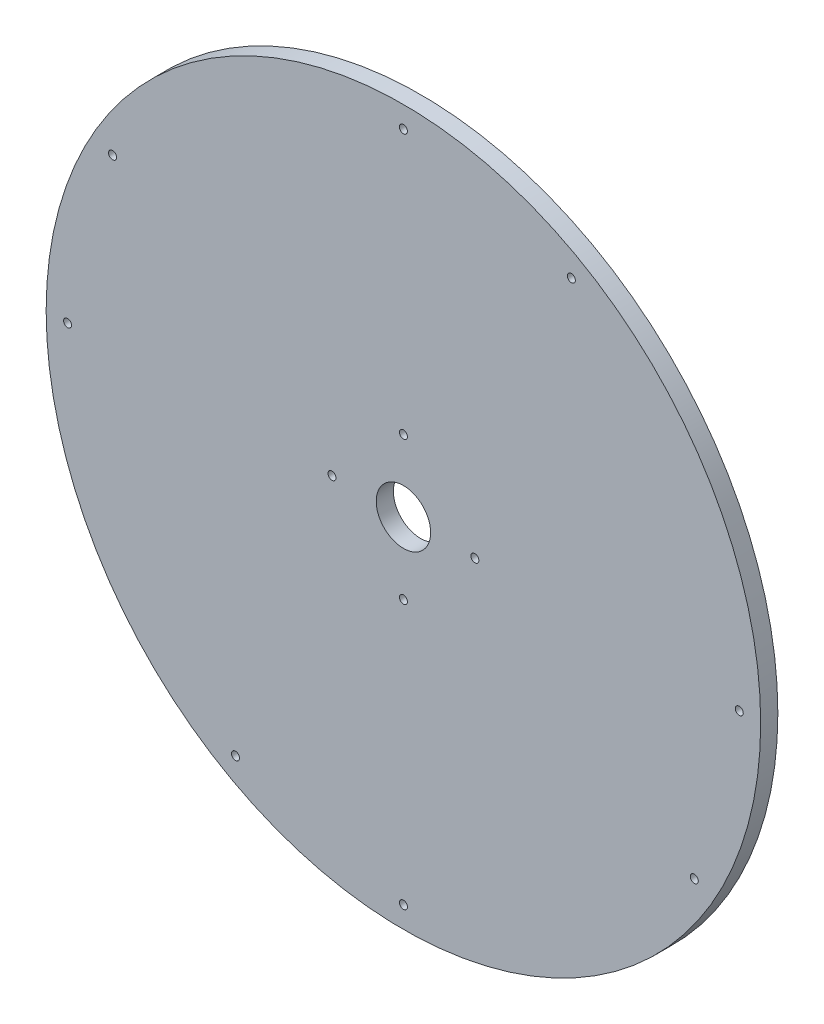
SolidWorks part; units mm, degrees
material "Pine"
ref_plane "Front Plane" through (0, 0, 0) normal (0, 0, 1) x (1, 0, 0)
ref_plane "Top Plane" through (0, 0, 0) normal (0, 1, 0) x (1, 0, 0)
ref_plane "Right Plane" through (0, 0, 0) normal (1, 0, 0) x (0, 0, -1)
sketch "Sketch1" plane through (0, 0, 0) normal (1, 0, 0) x (0, 0, -1)
  line L0 (0, 0) -> (33.6585, 0) construction
  line L1 (0, 125) -> (6, 125)
  line L2 (6, 125) -> (6, 9.525)
  line L3 (6, 9.525) -> (0, 9.525)
  line L4 (0, 9.525) -> (0, 125)
  dimension "D1" = 6
  dimension "D2" = 250
  dimension "D3" = 19.05
revolve "Revolve1" add sketch "Sketch1" angle 360 about L0
sketch "Sketch2" plane through (0, 0, 0) normal (0, 0, 1) x (1, 0, 0)
  line L0 (-58.75, -101.758) -> (58.75, 101.758) construction
  line L1 (101.758, -58.75) -> (-101.758, 58.75) construction
  line L2 (0, 117.5) -> (0, -117.5) construction
  circle A0 centre (0, 0) radius 25 construction
  circle A1 centre (0, 25) radius 1.4
  circle A2 centre (25, 0) radius 1.4
  circle A3 centre (0, -25) radius 1.4
  circle A4 centre (-25, 0) radius 1.4
  circle A5 centre (0, 0) radius 117.5 construction
  circle A6 centre (0, 117.5) radius 1.4
  circle A7 centre (0, -117.5) radius 1.4
  circle A8 centre (-117.5, 0) radius 1.4
  circle A9 centre (117.5, 0) radius 1.4
  circle A10 centre (58.75, 101.758) radius 1.4
  circle A11 centre (101.758, -58.75) radius 1.4
  circle A12 centre (-58.75, -101.758) radius 1.4
  circle A13 centre (-101.758, 58.75) radius 1.4
  dimension "D1" = 50
  dimension "D2" = 2.8
  dimension "D3" = 235
  dimension "D4" = 2.8
  dimension "D5" = 30
extrude "Cut-Extrude1" cut sketch "Sketch2" against normal up to next
